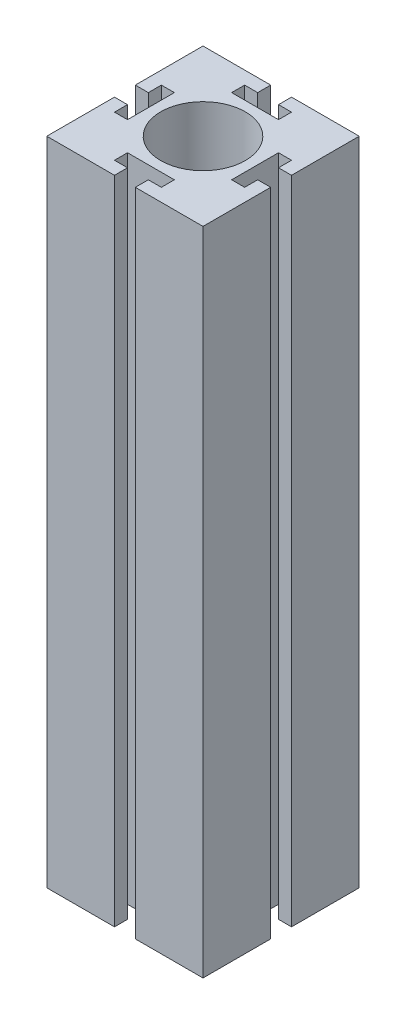
SolidWorks part; units mm, degrees
ref_plane "Plan de face" through (0, 0, 0) normal (0, 0, 1) x (1, 0, 0)
ref_plane "Plan de dessus" through (0, 0, 0) normal (0, 1, 0) x (1, 0, 0)
ref_plane "Plan de droite" through (0, 0, 0) normal (1, 0, 0) x (0, 0, -1)
sketch "Esquisse1" plane through (0, 0, 0) normal (0, 1, 0) x (1, 0, 0)
  line L1 (-6, 6) -> (6, 6)
  line L2 (-6, 6) -> (-6, -6)
  line L3 (-6, -6) -> (6, -6)
  line L4 (6, 6) -> (6, -6)
  dimension "D1" = 12
  dimension "D2" = 12
  dimension "D3" = 6
  dimension "D4" = 6
extrude "Boss.-Extru.1" add sketch "Esquisse1" along normal blind 50
sketch "Esquisse2" plane through (0, 50, 0) normal (0, 1, 0) x (1, 0, 0)
  line L0 (-5, -0.8) -> (-5, -1.8)
  line L1 (-6, 0.8) -> (-5, 0.8)
  line L2 (-6, 0.8) -> (-6, -0.8)
  line L3 (-6, -0.8) -> (-5, -0.8)
  line L5 (-5, 1.8) -> (-4, 1.8)
  line L6 (-5, 1.8) -> (-5, 0.8)
  line L7 (-5, -1.8) -> (-4, -1.8)
  line L8 (-4, 1.8) -> (-4, -1.8)
  line L9 (-6, 6) -> (-6, -6) construction
  line L10 (1.8, 5) -> (1.8, 4)
  line L11 (1.8, 4) -> (-1.8, 4)
  line L12 (-1.8, 5) -> (-1.8, 4)
  line L13 (-0.8, 5) -> (-1.8, 5)
  line L14 (-0.8, 6) -> (-0.8, 5)
  line L15 (0.8, 6) -> (-0.8, 6)
  line L16 (0.8, 6) -> (0.8, 5)
  line L17 (1.8, 5) -> (0.8, 5)
  line L18 (5, -1.8) -> (4, -1.8)
  line L19 (4, -1.8) -> (4, 1.8)
  line L20 (5, 1.8) -> (4, 1.8)
  line L21 (5, 0.8) -> (5, 1.8)
  line L22 (6, 0.8) -> (5, 0.8)
  line L23 (6, -0.8) -> (6, 0.8)
  line L24 (6, -0.8) -> (5, -0.8)
  line L25 (5, -1.8) -> (5, -0.8)
  line L26 (-1.8, -5) -> (-1.8, -4)
  line L27 (-1.8, -4) -> (1.8, -4)
  line L28 (1.8, -5) -> (1.8, -4)
  line L29 (0.8, -5) -> (1.8, -5)
  line L30 (0.8, -6) -> (0.8, -5)
  line L31 (-0.8, -6) -> (0.8, -6)
  line L32 (-0.8, -6) -> (-0.8, -5)
  line L33 (-1.8, -5) -> (-0.8, -5)
  point P38 (0, 0)
  dimension "D1" = 1.6
  dimension "D2" = 1
  dimension "D3" = 1
  dimension "D4" = 0
  dimension "D5" = 0.8
  dimension "D6" = 1
  dimension "D7" = 2
  dimension "D8" = 4
extrude "Enlèv. mat.-Extru.1" cut sketch "Esquisse2" against normal up to vertex (50 mm away) up to point (0, 0, 0)
sketch "Esquisse3" plane through (0, 50, 0) normal (0, 1, 0) x (1, 0, 0)
  circle A0 centre (0, 0) radius 3.25
  dimension "D1" = 6.5
extrude "Enlèv. mat.-Extru.2" cut sketch "Esquisse3" against normal blind 44
sketch "Esquisse4" plane through (0, 6, 0) normal (0, 1, 0) x (1, 0, 0)
  circle A0 centre (0, 0) radius 1
  dimension "D1" = 2
extrude "Enlèv. mat.-Extru.3" cut sketch "Esquisse4" against normal up to surface (6 mm away) up to face at (0, 0, 0)
chamfer "Chanfrein1" distance 3.5 distance2 3.5 1 edges at (0, 6, 1)
